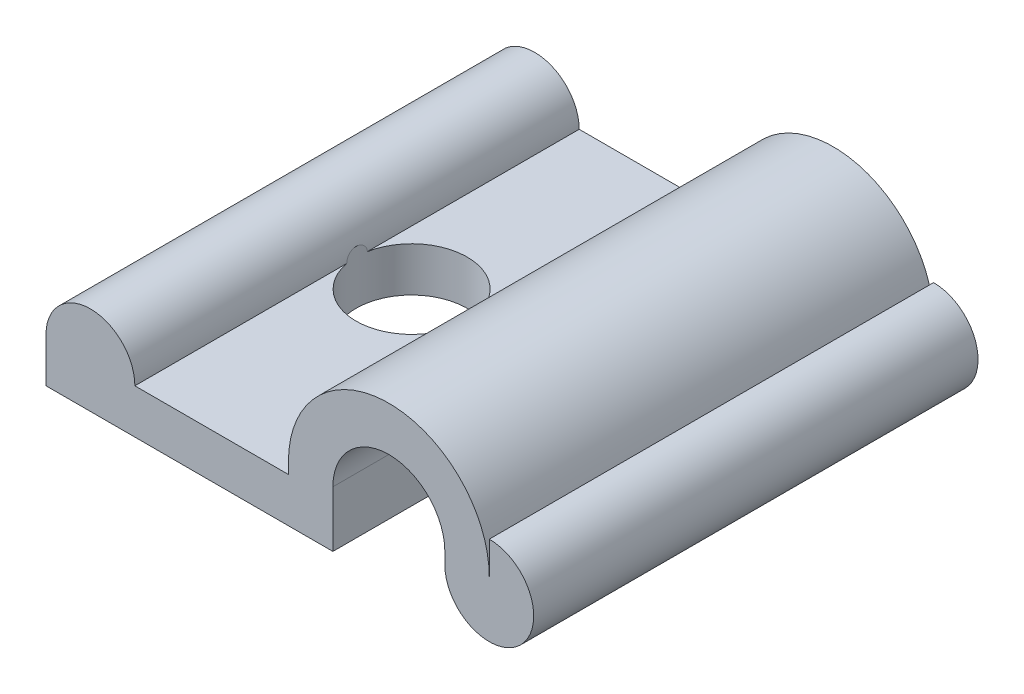
SolidWorks part; units mm, degrees
ref_plane "Front" through (0, 0, 0) normal (0, 0, 1) x (1, 0, 0)
ref_plane "Top" through (0, 0, 0) normal (0, 1, 0) x (1, 0, 0)
ref_plane "Right" through (0, 0, 0) normal (1, 0, 0) x (0, 0, -1)
sketch "Sketch1" plane through (0, 0, 0) normal (0, 0, 1) x (1, 0, 0)
  line L0 (-14.52, -0.66) -> (-5.74, -0.66)
  line L1 (5.74, 0) -> (5.74, 1.88)
  line L2 (3.2, 0) -> (3.2, -0.66)
  line L3 (-3.2, 0) -> (-3.2, -3.2)
  line L4 (-5.74, 0) -> (-5.74, -0.66)
  line L5 (-6.9, -0.66) -> (-6.9, -8.7588) construction
  line L6 (-3.2, -3.2) -> (-19.6, -3.2)
  line L7 (-19.6, -3.2) -> (-19.6, -0.66)
  line L8 (-14.52, -0.66) -> (-14.52, -3.2) construction
  line L9 (3.2, 0) -> (5.74, 0) construction
  arc A0 (3.2, 0) -> (-3.2, 0) centre (0, 0) ccw
  arc A1 (5.74, 0) -> (-5.74, 0) centre (0, 0) ccw
  arc A2 (3.2, -0.66) -> (5.74, 1.88) centre (5.74, -0.66) ccw
  arc A3 (-14.52, -0.66) -> (-19.6, -0.66) centre (-17.06, -0.66) ccw
  dimension "D1" = 6.4
  dimension "D2" = 2.54
  dimension "D4" = 2.54
  dimension "D6" = 27.88
  dimension "D3" = 8.94
  dimension "D8" = 6.9
  dimension "D9" = 12.7
extrude "Base-Extrude" add sketch "Sketch1" along normal mid plane 25.4
sketch "Sketch6" plane through (0, 0, 12.7) normal (0, 0, 1) x (1, 0, 0)
  point P0 (0, 0)
sketch "Sketch7" plane through (0, 0, -12.7) normal (0, 0, -1) x (-1, 0, 0)
  point P0 (0, 0)
ref_axis "Clip Axis" through (0, 0, 12.7) along (0, 0, -1)
other "RPoint1"
ref_axis "Axis1" through (0, 0, 7.7) along (0, 0, 1)
other "RPoint2"
ref_axis "Axis2" through (0, 0, -7.7) along (0, 0, -1)
sketch "FilterSketch" plane through (0, 0, 0) normal (0, 0, 1) x (1, 0, 0)
  circle A0 centre (0, 0) radius 3.2
  circle A1 centre (0, 0) radius 3.2
  circle A2 centre (0, 0) radius 2.35
  dimension "NominalDiameter" = 6.4
  dimension "InnerDiameter" = 4.7
  dimension "OuterDiameter" = 6.4
sketch "Sketch9" plane through (0, -3.2, 0) normal (0, -1, 0) x (1, 0, 0)
  line L0 (-19.6, 12.7) -> (-3.2, -12.7) construction
  circle A0 centre (-11.4, 0) radius 3.175
  dimension "D1" = 6.35
extrude "Cut-Extrude1" cut sketch "Sketch9" against normal through all
ref_axis "Axis of Revolution" through (-11.4, -0.0939, 0) along (0, -1, 0)
